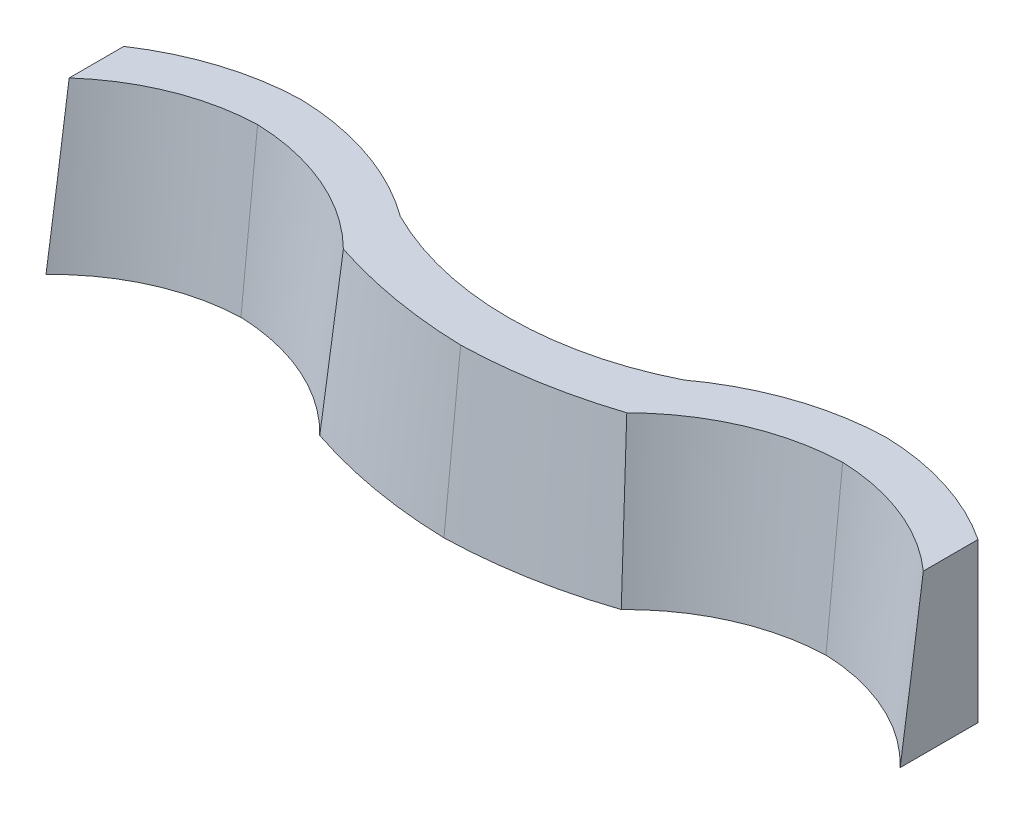
SolidWorks part; units mm, degrees
ref_plane "Front Plane" through (0, 0, 0) normal (0, 0, 1) x (1, 0, 0)
ref_plane "Top Plane" through (0, 0, 0) normal (0, 1, 0) x (1, 0, 0)
ref_plane "Right Plane" through (0, 0, 0) normal (1, 0, 0) x (0, 0, -1)
sketch "Sketch1" plane through (0, 0, 0) normal (0, 1, 0) x (1, 0, 0)
  line L0 (-110, -30) -> (-110, -41.2422) construction
  line L1 (-39.8399, -30) -> (34.8399, -30) construction
  line L2 (110, -30) -> (110, -41.2422) construction
  line L3 (0, -142.6423) -> (0, 36.4059) construction
  line L4 (0, -100) -> (0, 70) construction
  line L5 (-42.9151, -50) -> (42.9151, -50) construction
  line L6 (-110, -41.2422) -> (-39.8399, -43.9889) construction
  line L7 (39.8399, -43.9889) -> (110, -41.2422) construction
  line L8 (-110, -30) -> (-39.8399, -30) construction
  line L9 (110, -30) -> (34.8399, -30) construction
  line L10 (-39.8399, -30) -> (-39.8399, -43.9889) construction
  line L11 (34.8399, -30) -> (39.8399, -43.9889) construction
  arc A0 (-39.8399, -30) -> (34.8399, -30) centre (-2.5, 38.0274) ccw construction
  arc A1 (-39.8399, -43.9889) -> (0, -50) centre (-1.9011, 72.4289) ccw construction
  arc A2 (39.8399, -43.9889) -> (0, -50) centre (1.9011, 72.4289) cw construction
  dimension "D1" = 77.6015
  dimension "D2" = 122.4436
  dimension "D3" = 34.8399
  dimension "D4" = 70.1601
  dimension "D5" = 70.1601
  dimension "D6" = 92.242
  dimension "D7" = 13.9889
ref_plane "Bottom Of Chassis" through (0, -15, 0) normal (0, 1, 0) x (1, 0, 0)
ref_plane "Top of Chassis" through (0, 24, 0) normal (0, 1, 0) x (1, 0, 0)
sketch "Sketch3" plane through (0, 24, 0) normal (0, 1, 0) x (1, 0, 0)
  line L4 (110, -30) -> (110, -41.2422)
  line L6 (-71.9147, -28) -> (-71.9147, -17.3273) construction
  line L7 (0, -50) -> (0, -57.8303) construction
  line L8 (0, -142.6423) -> (0, 36.4059) construction
  line L9 (105, -41.2425) -> (105, -27.799)
  line L10 (-88.5863, -28) -> (-55.2431, -28) construction
  line L11 (-105, -41.2425) -> (-105, -27.799)
  line L12 (-110, 50) -> (-110, -30) construction
  line L13 (71.9147, -28) -> (71.9147, -17.3273) construction
  arc A0 (-34.8399, -30) -> (34.8399, -30) centre (0, 39.341) ccw
  arc A1 (0, -50) -> (34.8399, -43.9889) centre (-3.1802, 72.4023) ccw
  arc A2 (-34.8399, -43.9889) -> (-71.9147, -28) centre (-73.6989, -83.1159) ccw
  arc A3 (-71.9147, -28) -> (-105, -41.2425) centre (-70.2175, -80.192) ccw
  arc A4 (71.9147, -28) -> (105, -41.2425) centre (70.2175, -80.192) cw
  arc A5 (71.9147, -17.3273) -> (105, -27.799) centre (70.2175, -80.192) cw
  arc A6 (-34.8399, -30) -> (-71.9147, -17.3273) centre (-73.6989, -83.1159) ccw
  arc A7 (-71.9147, -17.3273) -> (-105, -27.799) centre (-70.2175, -80.192) ccw
  arc A8 (-71.9147, -17.3273) -> (-112.1058, -33.2855) centre (-70.2175, -80.192) ccw construction
  arc A9 (-29.276, -34.5574) -> (-71.9147, -17.3273) centre (-73.6989, -83.1159) ccw construction
  arc A10 (34.8399, -30) -> (71.9147, -17.3273) centre (73.6989, -83.1159) cw
  arc A11 (34.8399, -43.9889) -> (71.9147, -28) centre (73.6989, -83.1159) cw
  arc A16 (0, -50) -> (39.8399, -43.9889) centre (1.9011, 72.4289) ccw construction
  arc A18 (-34.8399, -43.9889) -> (0, -50) centre (3.1802, 72.4023) ccw
  arc A19 (-39.8399, -43.9889) -> (0, -50) centre (-1.9011, 72.4289) ccw construction
  arc A20 (-39.8399, -30) -> (34.8399, -30) centre (-2.5, 38.0274) ccw construction
  arc A21 (-29.276, -34.5574) -> (0, -39.3281) centre (3.1802, 72.4023) ccw construction
  arc A22 (0, -39.3281) -> (31.5274, -33.8482) centre (-3.1802, 72.4023) ccw construction
  dimension "D1" = 10.668
extrude "Boss-Extrude1" add sketch "Sketch3" against normal up to surface (39 mm away) contours A2 A18 A1 A11 A4 L9 L4 A5 A10 A0 A6 A7 L11 A3 region at (90.4117, 24, 29.7385) up to plane "Bottom Of Chassis"
draft "Draft2" type of draft neutral plane draft angle 6 faces to draft 6 face at (89.0397, 4.5, 33.1664) face at (52.6193, 4.5, 34.2369) face at (17.529, 4.5, 47.6265) face at (-89.0397, 4.5, 33.1664) face at (-52.6193, 4.5, 34.2369) face at (-17.529, 4.5, 47.6265) neutral plane through (0, 24, 0) neutral plane normal (0, 1, 0) parameters "D1"=6
